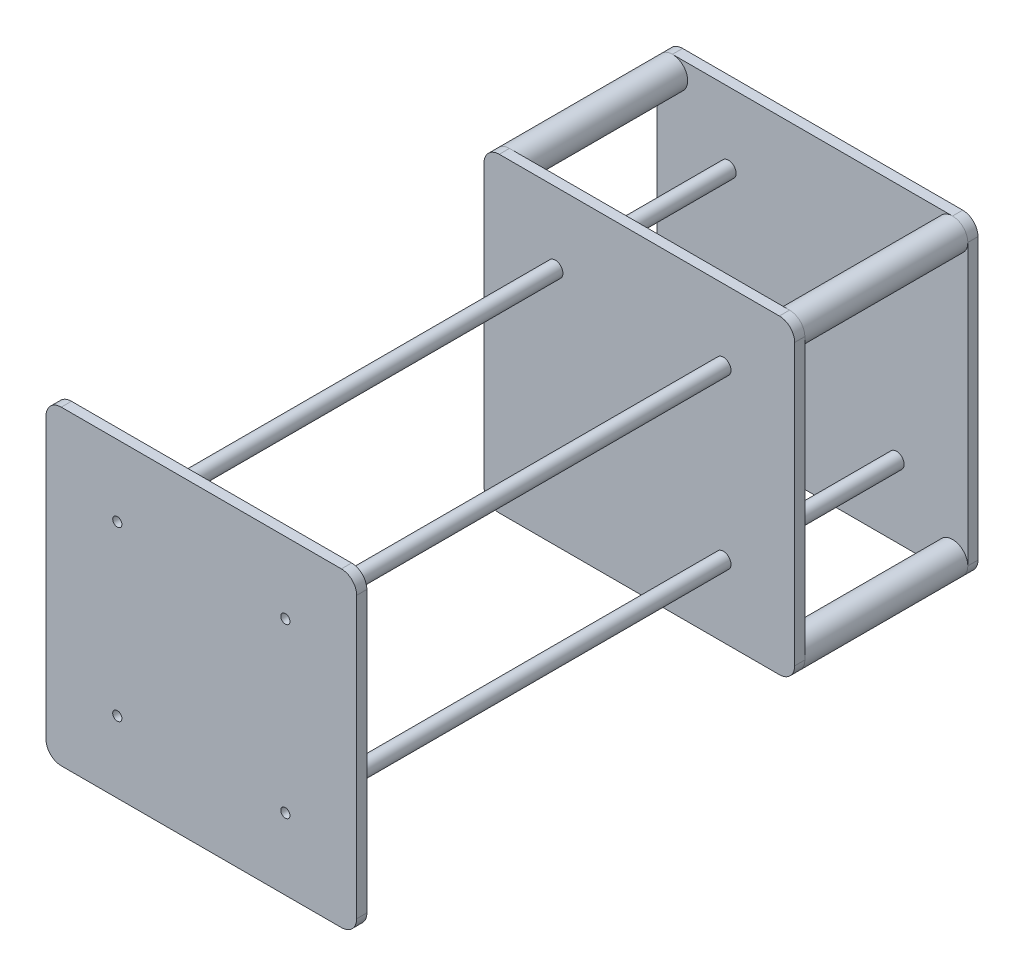
SolidWorks part; units mm, degrees
ref_plane "Plan de face" through (0, 0, 0) normal (0, 0, 1) x (1, 0, 0)
ref_plane "Plan de dessus" through (0, 0, 0) normal (0, 1, 0) x (1, 0, 0)
ref_plane "Plan de droite" through (0, 0, 0) normal (1, 0, 0) x (0, 0, -1)
sketch "Esquisse1" plane through (0, 0, 0) normal (0, 0, 1) x (1, 0, 0)
  line L1 (-152.5, -152.5) -> (152.5, -152.5)
  line L2 (-152.5, -152.5) -> (-152.5, 152.5)
  line L3 (-152.5, 152.5) -> (152.5, 152.5)
  line L4 (152.5, -152.5) -> (152.5, 152.5)
  dimension "D1" = 152.5
  dimension "D2" = 305
  dimension "D3" = 305
  dimension "D4" = 152.5
extrude "Boss.-Extru.1" add sketch "Esquisse1" along normal blind 10
sketch "Esquisse2" plane through (0, 0, 10) normal (0, 0, 1) x (1, 0, 0)
  line L0 (152.5, 152.5) -> (-152.5, 152.5) construction
  line L1 (152.5, -152.5) -> (152.5, 152.5) construction
  line L2 (-152.5, 152.5) -> (-152.5, -152.5) construction
  line L3 (-152.5, -152.5) -> (152.5, -152.5) construction
  circle A0 centre (137.5, 137.5) radius 15
  circle A1 centre (137.5, -137.5) radius 15
  circle A2 centre (-137.5, -137.5) radius 15
  circle A3 centre (-137.5, 137.5) radius 15
  dimension "D1" = 30
  dimension "3" = 30
  dimension "D2" = 30
  dimension "D3" = 30
extrude "Boss.-Extru.2" add sketch "Esquisse2" along normal blind 160
sketch "Esquisse3" plane through (0, 0, 170) normal (0, 0, 1) x (1, 0, 0)
  line L5 (152.5, -152.5) -> (152.5, 152.5) construction
  line L8 (152.5, -152.5) -> (-152.5, -152.5)
  line L9 (152.5, -152.5) -> (152.5, 152.5)
  line L10 (152.5, 152.5) -> (-152.5, 152.5)
  line L11 (-152.5, -152.5) -> (-152.5, 152.5)
  line L12 (-152.5, 152.5) -> (-152.5, -152.5) construction
  line L13 (-152.5, -152.5) -> (152.5, -152.5) construction
  line L14 (152.5, 152.5) -> (-152.5, 152.5) construction
extrude "Boss.-Extru.3" add sketch "Esquisse3" along normal blind 10
sketch "Esquisse4" plane through (0, 0, 180) normal (0, 0, 1) x (1, 0, 0)
  line L1 (90, -90) -> (-90, -90) construction
  line L2 (90, -90) -> (90, 90) construction
  line L3 (90, 90) -> (-90, 90) construction
  line L4 (-90, -90) -> (-90, 90) construction
  circle A0 centre (82.5, -82.5) radius 7.5
  circle A1 centre (-82.5, -82.5) radius 7.5
  circle A2 centre (82.5, 82.5) radius 7.5
  circle A3 centre (-82.5, 82.5) radius 7.5
  point P4 (0, 0)
  dimension "D5" = 15
  dimension "D6" = 15
  dimension "D7" = 15
  dimension "D8" = 15
  dimension "D1" = 90
  dimension "D2" = 180
  dimension "D3" = 180
  dimension "D4" = 90
extrude "Enlèv. mat.-Extru.1" cut sketch "Esquisse4" against normal through all
sketch "Esquisse5" plane through (0, 0, 0) normal (0, 0, -1) x (-1, 0, 0)
  circle A0 centre (-82.5, 82.5) radius 7.5
  circle A1 centre (82.5, 82.5) radius 7.5
  circle A2 centre (82.5, -82.5) radius 7.5
  circle A3 centre (-82.5, -82.5) radius 7.5
extrude "Boss.-Extru.4" add sketch "Esquisse5" against normal blind 600
sketch "Esquisse7" plane through (0, 0, 600) normal (0, 0, 1) x (1, 0, 0)
  line L0 (152.5, 152.5) -> (-152.5, 152.5) construction
  line L1 (-152.5, -152.5) -> (152.5, -152.5)
  line L2 (-152.5, -152.5) -> (-152.5, 152.5)
  line L3 (-152.5, 152.5) -> (152.5, 152.5)
  line L4 (152.5, -152.5) -> (152.5, 152.5)
  line L5 (-152.5, -152.5) -> (152.5, -152.5) construction
  line L6 (-152.5, 152.5) -> (-152.5, -152.5) construction
  line L7 (152.5, -152.5) -> (152.5, 152.5) construction
extrude "Boss.-Extru.5" add sketch "Esquisse7" along normal blind 10
hole_wizard "Dégagement M81" positions "Esquisse3D2" profile "Esquisse12" hole size "M8" standard "ISO"
sketch3d "Esquisse3D2"
  circle A0 centre (-82.5, -82.5, 180) radius 7.5 construction
  circle A1 centre (82.5, -82.5, 180) radius 7.5 construction
  circle A2 centre (-82.5, 82.5, 180) radius 7.5 construction
  circle A3 centre (82.5, 82.5, 180) radius 7.5 construction
  point P0 (82.5, -82.5, 610)
  point P2 (82.5, 82.5, 610)
  point P4 (-82.5, 82.5, 610)
  point P6 (-82.5, -82.5, 610)
  point P12 (-82.5, -82.5, 187.5)
  point P17 (82.5, -82.5, 187.5)
  point P21 (-82.5, 82.5, 187.5)
  point P25 (82.5, 82.5, 187.5)
sketch "Esquisse12" plane through (82.5, -82.5, 610) normal (1, 0, 0) x (0, -1, 0)
  line L0 (0, 0) -> (0, 12.7039)
  line L1 (0, 12.7039) -> (4.5, 10)
  line L2 (4.5, 10) -> (4.5, 0)
  line L5 (4.5, 0) -> (0, 0)
  line L10 (0, 12.7039) -> (-4.5, 10) construction
  line L11 (0, -6.35) -> (0, 107.95) construction
  dimension "Diamètre du perçage" = 9
  dimension "Profondeur du perçage" = 10
  dimension "Angle de pointe" = 118
fillet "Congé1" radius 15 12 edges at (-152.5, 152.5, 605) (-152.5, 152.5, 175) (-152.5, 152.5, 5) (-152.5, -152.5, 5) (-152.5, -152.5, 175) (-152.5, -152.5, 605) (152.5, -152.5, 605) (152.5, -152.5, 175) (152.5, -152.5, 5) (152.5, 152.5, 5) (152.5, 152.5, 175) (152.5, 152.5, 605)
sketch "Esquisse13" [suppressed] plane through (0, 0, 180) normal (0, 0, 1) x (1, 0, 0)
  circle A0 centre (-137.5, 137.5) radius 15
  circle A1 centre (137.5, -137.5) radius 15
  circle A2 centre (137.5, 137.5) radius 15
  circle A3 centre (-137.5, -137.5) radius 15
extrude "Boss.-Extru.6" [suppressed] add sketch "Esquisse13" along normal blind 0.1
sketch "Esquisse15" [suppressed] plane through (0, 0, 180) normal (0, 0, 1) x (1, 0, 0)
  circle A0 centre (0, 0) radius 20
  dimension "D1" = 40
extrude "Boss.-Extru.8" [suppressed] add sketch "Esquisse15" along normal blind 10 contours A0
hole_wizard "Dégagement M162" [suppressed] positions "Esquisse18" profile "Esquisse19" hole size "M16" standard "ISO"
sketch "Esquisse18" plane through (0, 0, 190) normal (0, 0, 1) x (1, 0, 0)
  point P0 (0, 0)
sketch "Esquisse19" plane through (0, 0, 190) normal (1, 0, 0) x (0, -1, 0)
  line L0 (0, 0) -> (0, 35.2575)
  line L1 (0, 35.2575) -> (8.75, 30)
  line L2 (8.75, 30) -> (8.75, 0)
  line L5 (8.75, 0) -> (0, 0)
  line L10 (0, 35.2575) -> (-8.75, 30) construction
  line L11 (0, -6.35) -> (0, 107.95) construction
  dimension "Diamètre du perçage" = 17.5
  dimension "Profondeur du perçage" = 30
  dimension "Angle de pointe" = 118
sketch "Esquisse20" [suppressed] plane through (0, 0, 180) normal (0, 0, 1) x (1, 0, 0)
  line L0 (7.5, -35) -> (-7.5, -35) construction
  line L1 (7.5, -45) -> (-7.5, -45)
  line L2 (7.5, -25) -> (-7.5, -25)
  line L3 (7.5, 35) -> (-7.5, 35) construction
  line L4 (7.5, 25) -> (-7.5, 25)
  line L5 (7.5, 45) -> (-7.5, 45)
  arc A0 (7.5, -45) -> (7.5, -25) centre (7.5, -35) ccw
  arc A1 (-7.5, -25) -> (-7.5, -45) centre (-7.5, -35) ccw
  arc A2 (7.5, 25) -> (7.5, 45) centre (7.5, 35) ccw
  arc A3 (-7.5, 45) -> (-7.5, 25) centre (-7.5, 35) ccw
  circle A4 centre (0, 0) radius 8.75 construction
  point P2 (0, -35)
  point P7 (0, 35)
  point P15 (0, 0)
  dimension "D3" = 15
  dimension "D1" = 50
  dimension "D2" = 35
  dimension "D4" = 20
extrude "Boss.-Extru.9" [suppressed] add sketch "Esquisse20" along normal blind 5
hole_wizard "Dégagement M163" [suppressed] positions "Esquisse3D4" profile "Esquisse21" hole size "M16" standard "ISO"
sketch3d "Esquisse3D4"
  point P0 (-0.0933, -34.8778, 185)
  point P2 (-0.4731, 35.1818, 185)
sketch "Esquisse21" plane through (-0.0933, -34.8778, 185) normal (1, 0, 0) x (0, -1, 0)
  line L0 (0, 0) -> (0, 35.2575)
  line L1 (0, 35.2575) -> (8.75, 30)
  line L2 (8.75, 30) -> (8.75, 0)
  line L5 (8.75, 0) -> (0, 0)
  line L10 (0, 35.2575) -> (-8.75, 30) construction
  line L11 (0, -6.35) -> (0, 107.95) construction
  dimension "Diamètre du perçage" = 17.5
  dimension "Profondeur du perçage" = 30
  dimension "Angle de pointe" = 118
